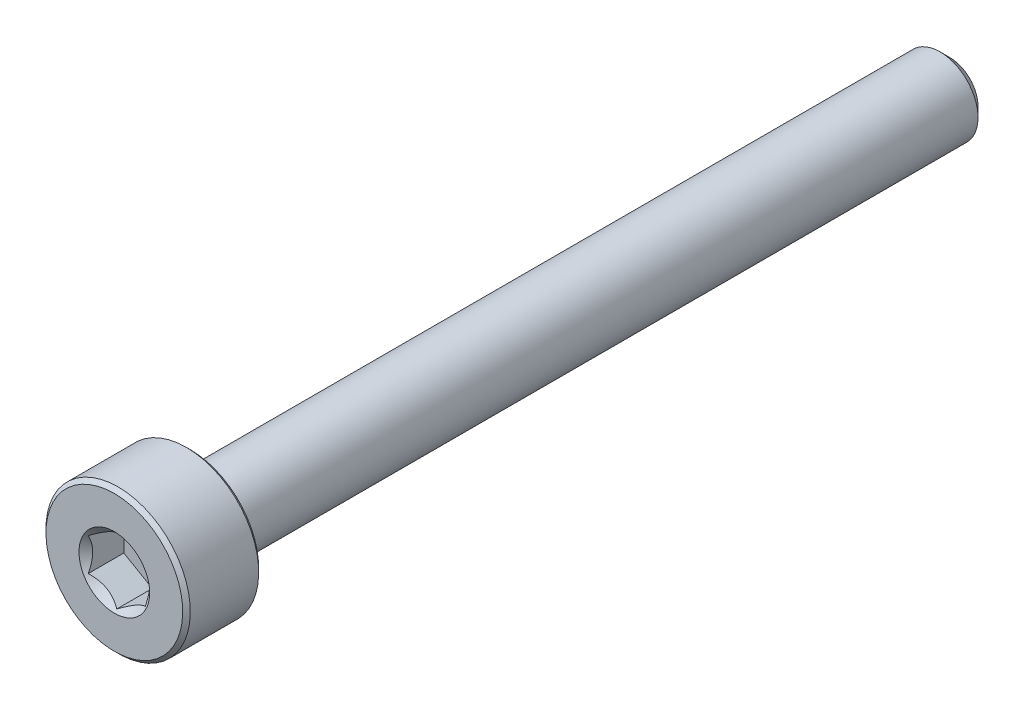
SolidWorks part; units mm, degrees
ref_plane "Front Plane" through (0, 0, 0) normal (0, 0, 1) x (1, 0, 0)
ref_plane "Top Plane" through (0, 0, 0) normal (0, 1, 0) x (1, 0, 0)
ref_plane "Right Plane" through (0, 0, 0) normal (1, 0, 0) x (0, 0, -1)
sketch "Sketch1" plane through (0, 0, 0) normal (1, 0, 0) x (0, 0, -1)
  line L0 (-11, 0) -> (11, 0) construction
  line L1 (11, 0) -> (11, 0.7402) construction
  line L2 (11, 0.7402) -> (10.7402, 1) construction
  line L3 (10.7402, 1) -> (10.7, 1) construction
  line L4 (10.7, 1) -> (-9, 1) construction
  line L5 (-9, 1) -> (-9, 1.9) construction
  line L6 (-9, 1.9) -> (-11, 1.9) construction
  line L7 (-11, 1.9) -> (-11, 0) construction
  line L8 (11, 0.7402) -> (11, 1) construction
  line L9 (10.975, 1.0433) -> (11.175, 0.6969) construction
  line L10 (11.175, 0.6969) -> (11.375, 1.0433) construction
  line L11 (11.375, 1.0433) -> (10.975, 1.0433) construction
  line L12 (11.175, 1.0433) -> (11.175, 1) construction
  line L13 (11.175, 0.6969) -> (11.175, 0.7402) construction
  line L14 (11.15, 0.7402) -> (11.2, 0.7402) construction
  line L15 (11, 1) -> (11.35, 1) construction
  line L16 (10.9875, 1.0217) -> (11.3625, 1.0217) construction
  line L17 (11, 0) -> (11, -1) construction
  line L18 (-9.1, 1.9) -> (-9, 1.8) construction
  line L19 (-10.9, 1.9) -> (-11, 1.8) construction
  line L20 (-9, 1) -> (-9, 0) construction
  line L21 (-9, 0.5) -> (-2.3333, 0.5) construction
  line L22 (-2.3333, 0.5) -> (4.3333, 0.5) construction
  line L23 (4.3333, 0.5) -> (11, 0.5) construction
  line L24 (-2.3333, 0.5) -> (-2.3333, 1) construction
  line L25 (-2.3333, 1) -> (-2.3333, 1.9) construction
  line L26 (4.3333, 0.5) -> (4.3333, 1.9) construction
  point P0 (-11, 0.75)
  point P3 (10, 1)
  point P4 (0, 0)
  point P18 (4.3333, 1)
  point P22 (11.175, 0.7402)
  point P24 (10.7, 1)
  point P25 (11.175, 1)
  point P28 (11.175, 1.0217)
  point P29 (10, -1)
  point P30 (-2.3333, 1)
  point P31 (-10, 1.9)
  point P37 (-9.35, 1.9)
  point P38 (-10.85, 1.9)
  point P45 (-2.3333, 0.5)
  point P46 (4.3333, 0.5)
  dimension "D2" = 0.05
  dimension "D7" = 0.1
  dimension "D8" = 0.1
  dimension "D9" = 0.1
  dimension "D10" = 0.05
  dimension "D11" = 0.25
  dimension "Drive Size" = 1.5
  dimension "Head Diameter" = 3.8
  dimension "Head Height" = 2
  dimension "Thread Pitch" = 0.4
  dimension "Thread Dia" = 2
  dimension "Length" = 20
  dimension "D12" = 0.3
  dimension "D4" = 1
  dimension "D3" = 45
sketch "Sketch2" plane through (0, 0, 0) normal (1, 0, 0) x (0, 0, -1)
  line L0 (-11, 0) -> (-11, 1.8)
  line L1 (-10.9, 1.9) -> (-9.1, 1.9)
  line L2 (-9, 1.8) -> (-9, 1.1)
  line L4 (10.7402, 1) -> (11, 0.7402)
  line L5 (11, 0.7402) -> (11, 0)
  line L6 (-9, 1.9) -> (-11, 1.9) construction
  line L7 (11, 0) -> (-11, 0)
  line L8 (-10.9, 1.9) -> (-11, 1.8) construction
  line L10 (-10.9, 1.9) -> (-11, 1.8)
  line L14 (-9.1, 1.9) -> (-9, 1.8) construction
  line L16 (-9.1, 1.9) -> (-9, 1.8)
  line L17 (-9, 1) -> (-9, 1.9) construction
  line L19 (-8.9, 1) -> (10.7402, 1)
  line L20 (10.7, 1) -> (-9, 1) construction
  arc A1 (-9, 1.1) -> (-8.9, 1) centre (-8.9, 1.1) ccw
  dimension "D3" = 0.1
revolve "Revolve1" add sketch "Sketch2" angle 360 about L7
sketch "Sketch3" plane through (0, 0, 11) normal (0, 0, 1) x (1, 0, 0)
  line L1 (0.75, -0.433) -> (0.75, 0.433)
  line L2 (0.75, 0.433) -> (0, 0.866)
  line L3 (0, 0.866) -> (-0.75, 0.433)
  line L4 (-0.75, 0.433) -> (-0.75, -0.433)
  line L5 (-0.75, -0.433) -> (0, -0.866)
  line L6 (0, -0.866) -> (0.75, -0.433)
  circle A0 centre (0, 0) radius 0.75 construction
  circle A1 centre (0, 0) radius 1.9 construction
  circle A2 centre (0, 0) radius 1.9 construction
  circle A3 centre (0, 0) radius 0.866 construction
  point P13 (0, 0)
  dimension "D1" = 1.7321
extrude "Cut-Extrude1" cut sketch "Sketch3" against normal offset from surface (1 mm away) 1 up to face at (0, 1.8, 9)
sketch "Sketch4" plane through (0, 0, 11) normal (0, 0, 1) x (1, 0, 0)
  circle A0 centre (0, 0) radius 0.931
  dimension "D1" = 1.862
extrude "Cut-Extrude2" cut sketch "Sketch4" against normal up to vertex (1 mm away) draft 45 up to point (0, 1.9, 10)
sketch "Sketch11" plane through (0, 0, 0) normal (1, 0, 0) x (0, 0, -1)
  line L0 (-11, 0) -> (11, 0) construction
  line L1 (-11, 0) -> (11, 0) construction
  line L2 (-5.25, 0) -> (-5.25, 1) construction
  line L3 (10.7, 1) -> (-9, 1) construction
  line L4 (7.25, 0) -> (7.25, 1) construction
  line L6 (11, 0.7402) -> (11, 1) construction
  point P2 (-5.25, 0)
  point P3 (7.25, 0)
  dimension "D1" = 3.75
  dimension "D2" = 3.75
sketch "Sketch6" [suppressed] plane through (0, 0, -11) normal (0, 0, -1) x (-1, 0, 0)
  circle A0 centre (0, 0) radius 1
curve "Helix/Spiral1" [suppressed] pitch 0.4 height 20.4 turns 51
sketch "Sketch10" [suppressed] plane through (0, 0, 0) normal (1, 0, 0) x (0, 0, -1)
  line L0 (-8.9, -1.9) -> (-8.9, 1.9)
  line L5 (-11, 0) -> (11, 0) construction
  line L6 (-8.9, 1) -> (-8.9, -1) construction
  point P3 (-8.9, 0)
split "Split1" [suppressed] bodies to split 106
sketch "Sketch7" [suppressed] plane through (0, 0, 0) normal (1, 0, 0) x (0, 0, -1)
  line L0 (10.9875, 1.0217) -> (11.3625, 1.0217)
  line L1 (11.3625, 1.0217) -> (11.2, 0.7402)
  line L2 (11.2, 0.7402) -> (11.15, 0.7402)
  line L3 (11.15, 0.7402) -> (10.9875, 1.0217)
sweep "Cut-Sweep1" [suppressed] cut profiles "Sketch7" path "Helix/Spiral1"
sketch "Sketch8" [suppressed] plane through (0, 0, 0) normal (1, 0, 0) x (0, 0, -1)
  line L0 (-9, 0) -> (-9, 1)
  line L1 (-8.9, -1) -> (-8.9, 1) construction
  line L2 (-9, 1) -> (-8.9, 1)
  line L4 (-8.9, 1) -> (-8.3226, 0)
  line L5 (-8.3226, 0) -> (-9, 0)
  line L6 (10.7, 1) -> (-9, 1) construction
  line L7 (-11, 0) -> (11, 0) construction
  dimension "D1" = 60
revolve "Revolve2" [suppressed] add sketch "Sketch8" angle 360 about L5
equation "\"D2@Sketch1\" = \"Thread Pitch@Sketch1\" / 8"
equation "\"D4@Helix/Spiral1\" = \"Thread Pitch@Sketch1\""
equation "\"D7@Sketch1\" = \"Head Height@Sketch1\" * .05"
equation "\"D8@Sketch1\"=\"D7@Sketch1\""
equation "\"D9@Sketch1\"=\"D7@Sketch1\""
equation "\"D10@Sketch1\"=\"D7@Sketch1\"/2"
equation "\"D11@Sketch1\"=\"D10@Sketch1\"*5"
equation "\"D4@Sketch1\"=\"Thread Pitch@Sketch1\"*2.5"
equation "\"D12@Sketch1\"=\"Thread Pitch@Sketch1\"*.75"
equation "\"D3@Helix/Spiral1\"=\"Length@Sketch1\"+\"Thread Pitch@Sketch1\""
equation "\"D3@Sketch2\"=\"Thread Dia@Sketch1\"*0.05"
equation "\"D1@Sketch11\"=\"Length@Sketch1\"*0.1875"
equation "\"D2@Sketch11\"=\"D1@Sketch11\""
equation "\"D1@Sketch4\"=\"D1@Sketch3\"*1.075"
